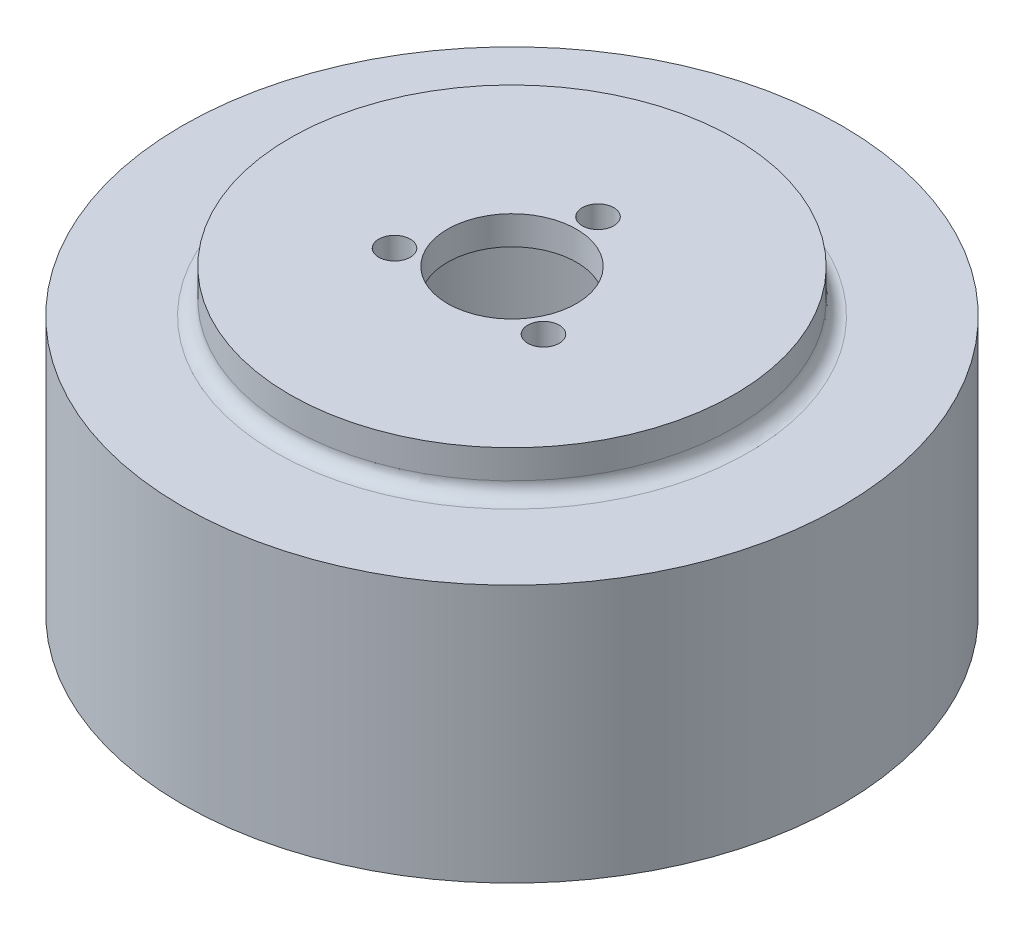
SolidWorks part; units mm, degrees
material "PUR"
ref_plane "Front Plane" through (0, 0, 0) normal (0, 0, 1) x (1, 0, 0)
ref_plane "Top Plane" through (0, 0, 0) normal (0, 1, 0) x (1, 0, 0)
ref_plane "Right Plane" through (0, 0, 0) normal (1, 0, 0) x (0, 0, -1)
sketch "Sketch1" plane through (0, 0, 0) normal (0, 1, 0) x (1, 0, 0)
  circle A0 centre (0, 0) radius 23
  dimension "D1" = 46
extrude "Boss-Extrude1" add sketch "Sketch1" along normal mid plane 21
sketch "Sketch2" plane through (0, -10.5, 0) normal (0, -1, 0) x (1, 0, 0)
  circle A0 centre (0, 0) radius 13.65
  dimension "D1" = 27.3
extrude "Cut-Extrude1" cut sketch "Sketch2" against normal offset from surface (19 mm away) 2 up to face at (0, 10.5, 23)
sketch "Sketch3" plane through (0, 10.5, 0) normal (0, 1, 0) x (1, 0, 0)
  line L0 (0, 0) -> (0, 6) construction
  line L1 (0, 0) -> (5.1962, -3) construction
  line L2 (0, 0) -> (-5.1962, -3) construction
  circle A0 centre (0, 0) radius 4.5
  point P8 (0, 0)
  dimension "D1" = 9
  dimension "D2" = 6
  dimension "D3" = 3
extrude "Cut-Extrude2" cut sketch "Sketch3" against normal through all
hole_wizard "M2 Clearance Hole1" positions "Sketch4" profile "Sketch5" hole size "M2" standard "ANSI Metric" end condition through all
sketch "Sketch4" plane through (0, 10.5, 0) normal (0, 1, 0) x (1, 0, 0)
  point P0 (0, 6)
  point P3 (-5.1962, -3)
  point P6 (5.1962, -3)
sketch "Sketch5" plane through (0, 10.5, -6) normal (1, 0, 0) x (0, 0, 1)
  line L0 (0, 0) -> (0, 21)
  line L1 (0, 21) -> (1.1, 21)
  line L2 (1.1, 21) -> (1.1, 0)
  line L5 (1.1, 0) -> (0, 0)
  line L11 (0, -6.35) -> (0, 107.95) construction
  dimension "Thru Hole Dia." = 2.2
  dimension "Thru Hole Depth" = 21
sketch "Sketch6" plane through (0, 10.5, 0) normal (0, 1, 0) x (1, 0, 0)
  circle A0 centre (0, 0) radius 15.5
  circle A1 centre (0, 0) radius 23 construction
  circle A2 centre (0, 0) radius 23
  dimension "D1" = 7.5
extrude "Cut-Extrude3" cut sketch "Sketch6" against normal blind 3
fillet "Fillet1" radius 1 1 edges at (0, 7.5, 15.5)
